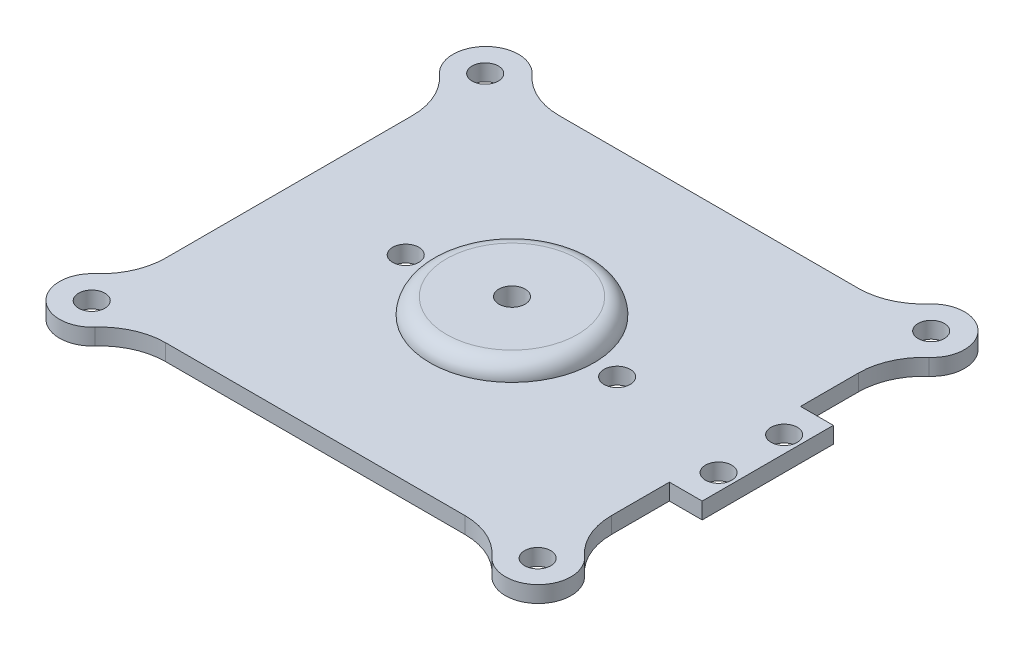
SolidWorks part; units mm, degrees
material "Zoltek Panex 33"
ref_plane "Alzado" through (0, 0, 0) normal (0, 0, 1) x (1, 0, 0)
ref_plane "Planta" through (0, 0, 0) normal (0, 1, 0) x (1, 0, 0)
ref_plane "Vista lateral" through (0, 0, 0) normal (1, 0, 0) x (0, 0, -1)
sketch "Croquis1" plane through (0, 0, 0) normal (0, 1, 0) x (1, 0, 0)
  line L0 (0, 0) -> (78, 0) construction
  line L1 (78, 60) -> (78, -60)
  line L2 (68, -70) -> (-68, -70)
  line L3 (-78, -60) -> (-78, 60)
  line L4 (-68, 70) -> (68, 70)
  arc A0 (-68, -70) -> (-78, -60) centre (-68, -60) cw
  arc A1 (68, -70) -> (78, -60) centre (68, -60) ccw
  arc A2 (78, 60) -> (68, 70) centre (68, 60) ccw
  arc A3 (-78, 60) -> (-68, 70) centre (-68, 60) cw
  point P5 (78, 0)
  point P7 (0, 70)
  dimension "D5" = 10
  dimension "D1" = 78
  dimension "D2" = 78
  dimension "D3" = 70
  dimension "D4" = 70
extrude "Saliente-Extruir1" add sketch "Croquis1" along normal blind 5
sketch "Croquis3" plane through (0, 5, 0) normal (0, 1, 0) x (1, 0, 0)
  circle A1 centre (0, 0) radius 25
  dimension "D1" = 50
extrude "Saliente-Extruir2" add sketch "Croquis3" along normal blind 5
sketch "Croquis4" plane through (0, 10, 0) normal (0, 1, 0) x (1, 0, 0)
  circle A1 centre (0, 0) radius 4
  dimension "D1" = 8
extrude "Cortar-Extruir1" cut sketch "Croquis4" against normal up to next
sketch "Croquis5" plane through (0, 5, 0) normal (0, 1, 0) x (1, 0, 0)
  line L0 (-68, -60.1711) -> (-68, 59.8289) construction
  line L1 (-68, 59.8289) -> (68, 59.8289) construction
  line L2 (68, 59.8289) -> (68, -60.1711) construction
  line L3 (-68, -60.1711) -> (68, -60.1711) construction
  line L4 (-32.24, -0.1711) -> (32.24, -0.1711) construction
  circle A0 centre (-68, -60.1711) radius 4
  circle A1 centre (-68, 59.8289) radius 4
  circle A2 centre (68, -60.1711) radius 4
  circle A3 centre (68, 59.8289) radius 4
  circle A4 centre (32.24, -0.1711) radius 4
  circle A5 centre (-32.24, -0.1711) radius 4
  point P11 (0, -0.1711)
  dimension "D1" = 8
  dimension "D2" = 8
  dimension "D3" = 8
  dimension "D4" = 8
  dimension "D5" = 120
  dimension "D6" = 136
extrude "Cortar-Extruir2" cut sketch "Croquis5" against normal up to next
sketch "Croquis12" plane through (0, 5, 0) normal (0, 1, 0) x (1, 0, 0)
  line L16 (68, -70) -> (-68, -70)
  line L17 (78, -60) -> (78, 60)
  line L22 (68, 70) -> (-68, 70)
  line L23 (-78, -60) -> (-78, 60)
  line L28 (78, -70) -> (-78, 70) construction
  line L29 (78, 70) -> (-78, -70) construction
  line L30 (45.6393, -60) -> (-45.6393, -60)
  line L35 (45.6393, 60) -> (-45.6393, 60)
  line L36 (68, 37.6393) -> (68, 20)
  line L41 (-68, 37.6393) -> (-68, -37.6393)
  line L42 (68, 60) -> (-68, -60) construction
  line L47 (68, -60) -> (-68, 60) construction
  line L48 (68, 20) -> (78, 20)
  line L49 (78, 20) -> (78, -20)
  line L50 (78, -20) -> (68, -20)
  line L51 (68, -20) -> (68, -37.6393)
  line L52 (73, -20) -> (73, 20) construction
  line L53 (73, 0) -> (73, -10) construction
  line L54 (73, 0) -> (73, 10) construction
  arc A25 (78, 60) -> (68, 70) centre (68, 60) ccw
  arc A44 (-68, 70) -> (-78, 60) centre (-68, 60) ccw
  arc A56 (-78, -60) -> (-68, -70) centre (-68, -60) ccw
  arc A57 (78, -60) -> (68, -70) centre (68, -60) cw
  arc A58 (-60.5464, 66.6667) -> (-74.6667, 52.5464) centre (-68, 60) ccw
  arc A59 (74.6667, 52.5464) -> (60.5464, 66.6667) centre (68, 60) ccw
  arc A60 (60.5464, -66.6667) -> (74.6667, -52.5464) centre (68, -60) ccw
  arc A61 (60.5016, -53.3838) -> (60.0695, -53.9085) centre (68, -60) ccw
  arc A62 (-74.6667, -52.5464) -> (-60.5464, -66.6667) centre (-68, -60) ccw
  arc A63 (74.6667, 52.5464) -> (68, 37.6393) centre (88, 37.6393) ccw
  arc A64 (60.5464, 66.6667) -> (45.6393, 60) centre (45.6393, 80) cw
  arc A65 (-60.5464, 66.6667) -> (-45.6393, 60) centre (-45.6393, 80) ccw
  arc A66 (-74.6667, 52.5464) -> (-68, 37.6393) centre (-88, 37.6393) cw
  arc A67 (-68, -37.6393) -> (-74.6667, -52.5464) centre (-88, -37.6393) cw
  arc A68 (-45.6393, -60) -> (-60.5464, -66.6667) centre (-45.6393, -80) ccw
  arc A69 (45.6393, -60) -> (60.5464, -66.6667) centre (45.6393, -80) cw
  arc A70 (74.6667, -52.5464) -> (68, -37.6393) centre (88, -37.6393) cw
  circle A71 centre (73, -10) radius 4
  circle A72 centre (73, 10) radius 4
  point P0 (0, 0)
  point P17 (0, 0)
  point P50 (68, 0)
  line M77 (-68, -70) -> (68, -70)
  line M79 (78, -60) -> (78, 60)
  line M81 (68, 70) -> (-68, 70)
  line M83 (-78, 60) -> (-78, -60)
  dimension "D1" = 10
  dimension "D2" = 20
  dimension "D3" = 20
extrude "Cortar-Extruir8" cut sketch "Croquis12" against normal up to next contours A58 A65 L35 A64 A59 M81 | A67 L41 A66 A58 A62 M83 | A69 L30 A68 A62 A60 M77 | A70 A60 L50 L51 M79 | A59 A63 L36 L48 L17 | A72 | A71 region at (0, 5, 65.2141) region at (73.4122, 5, 35.4488) region at (-73.2482, 5, 0) region at (73.4122, 5, -35.4488) region at (0, 5, -65.2141) region at (73, 5, 10) region at (73, 5, -10)
fillet "Redondeo2" radius 5 1 edges at (0, 10, 25)
sketch "Croquis13" plane through (0, 0, 0) normal (0, 0, 1) x (1, 0, 0)
  line L0 (0, 0) -> (0, -15) construction
  line L1 (-50, -15) -> (50, -15) construction
  circle A0 centre (0, -15) radius 4
  circle A1 centre (-50, -15) radius 4
  circle A2 centre (50, -15) radius 4
  point P6 (0, -15)
  dimension "D1" = 100
  dimension "D2" = 15
